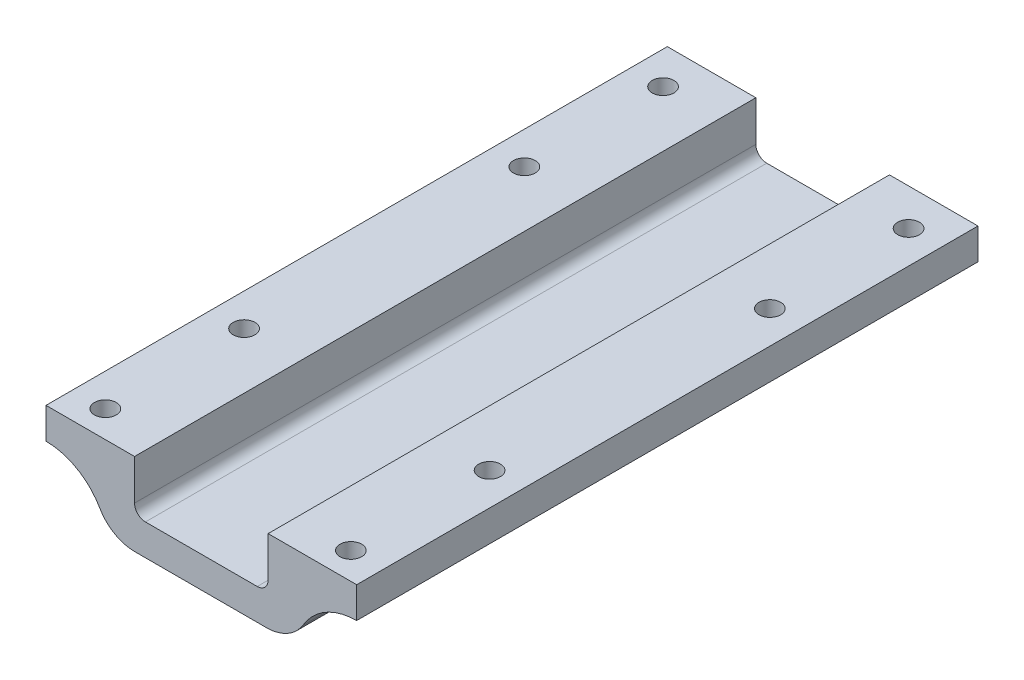
SolidWorks part; units mm, degrees
ref_plane "Front Plane" through (0, 0, 0) normal (0, 0, 1) x (1, 0, 0)
ref_plane "Top Plane" through (0, 0, 0) normal (0, 1, 0) x (1, 0, 0)
ref_plane "Right Plane" through (0, 0, 0) normal (1, 0, 0) x (0, 0, -1)
sketch "Sketch1" plane through (0, 0, 0) normal (0, 0, 1) x (1, 0, 0)
  line L0 (15, 13.2239) -> (35, 13.2239) construction
  line L1 (50, 10.2246) -> (50, 5.2246)
  line L2 (35.75, 10.2246) -> (50, 10.2246)
  line L3 (35.75, 3.7246) -> (35.75, 10.2246)
  line L4 (15, 22.2239) -> (15, 4.2239)
  line L5 (16, 3.2239) -> (34, 3.2239)
  line L6 (35, 4.2239) -> (35, 22.2239)
  line L7 (34, 23.2239) -> (16, 23.2239)
  line L8 (15, 22.2239) -> (15, 4.2239) construction
  line L9 (16, 3.2239) -> (34, 3.2239) construction
  line L10 (35, 4.2239) -> (35, 22.2239) construction
  line L11 (34, 23.2239) -> (16, 23.2239) construction
  line L12 (16, 1.9746) -> (34, 1.9746)
  line L13 (14.25, 10.2246) -> (14.25, 3.7246)
  line L14 (0, 10.2246) -> (14.25, 10.2246)
  line L15 (0, 5.2246) -> (0, 10.2246)
  line L16 (37.0096, 28.7233) -> (12.9904, 28.7233)
  line L17 (0, 21.2233) -> (0, 16.2233)
  line L18 (0, 16.2233) -> (14.25, 16.2233)
  line L19 (14.25, 16.2233) -> (14.25, 22.7233)
  line L20 (16, 24.4733) -> (34, 24.4733)
  line L21 (35.75, 22.7233) -> (35.75, 16.2233)
  line L22 (35.75, 16.2233) -> (50, 16.2233)
  line L23 (50, 16.2233) -> (50, 21.2233)
  line L24 (37.0096, 28.7233) -> (12.9904, 28.7233) construction
  line L25 (0, 21.2233) -> (0, 16.2233) construction
  line L26 (0, 16.2233) -> (14.25, 16.2233) construction
  line L27 (14.25, 16.2233) -> (14.25, 22.7233) construction
  line L28 (16, 24.4733) -> (34, 24.4733) construction
  line L29 (35.75, 22.7233) -> (35.75, 16.2233) construction
  line L30 (35.75, 16.2233) -> (50, 16.2233) construction
  line L31 (50, 16.2233) -> (50, 21.2233) construction
  line L33 (14.2894, -3.0254) -> (35.7106, -3.0254)
  arc A1 (41.3397, 0.2246) -> (50, 5.2246) centre (50, -4.7754) cw
  arc A2 (35.75, 3.7246) -> (34, 1.9746) centre (34, 3.7246) cw
  arc A3 (16, 1.9746) -> (14.25, 3.7246) centre (16, 3.7246) cw
  arc A4 (16, 23.2239) -> (15, 22.2239) centre (16, 22.2239) ccw
  arc A5 (15, 4.2239) -> (16, 3.2239) centre (16, 4.2239) ccw
  arc A6 (34, 3.2239) -> (35, 4.2239) centre (34, 4.2239) ccw
  arc A7 (35, 22.2239) -> (34, 23.2239) centre (34, 22.2239) ccw
  arc A8 (16, 23.2239) -> (15, 22.2239) centre (16, 22.2239) ccw construction
  arc A9 (15, 4.2239) -> (16, 3.2239) centre (16, 4.2239) ccw construction
  arc A10 (34, 3.2239) -> (35, 4.2239) centre (34, 4.2239) ccw construction
  arc A11 (35, 22.2239) -> (34, 23.2239) centre (34, 22.2239) ccw construction
  arc A12 (0, 5.2246) -> (8.6603, 0.2246) centre (0, -4.7754) cw
  arc A14 (12.9904, 28.7233) -> (8.6603, 26.2233) centre (12.9904, 23.7233) ccw
  arc A15 (0, 21.2233) -> (8.6603, 26.2233) centre (0, 31.2233) ccw
  arc A16 (16, 24.4733) -> (14.25, 22.7233) centre (16, 22.7233) ccw
  arc A17 (35.75, 22.7233) -> (34, 24.4733) centre (34, 22.7233) ccw
  arc A18 (41.3397, 26.2233) -> (50, 21.2233) centre (50, 31.2233) ccw
  arc A19 (41.3397, 26.2233) -> (37.0096, 28.7233) centre (37.0096, 23.7233) ccw
  arc A20 (12.9904, 28.7233) -> (8.6603, 26.2233) centre (12.9904, 23.7233) ccw construction
  arc A21 (0, 21.2233) -> (8.6603, 26.2233) centre (0, 31.2233) ccw construction
  arc A22 (16, 24.4733) -> (14.25, 22.7233) centre (16, 22.7233) ccw construction
  arc A23 (35.75, 22.7233) -> (34, 24.4733) centre (34, 22.7233) ccw construction
  arc A24 (41.3397, 26.2233) -> (50, 21.2233) centre (50, 31.2233) ccw construction
  arc A25 (41.3397, 26.2233) -> (37.0096, 28.7233) centre (37.0096, 23.7233) ccw construction
  arc A26 (8.6603, 0.2246) -> (14.2894, -3.0254) centre (14.2894, 3.4746) ccw
  arc A27 (35.7106, -3.0254) -> (41.3397, 0.2246) centre (35.4411, 3.9414) ccw
  point P52 (25, -3.0254)
  point P53 (25, 1.9746)
  dimension "D3" = 5
  dimension "D1" = 0
  dimension "D2" = 0
extrude "Boss-Extrude1" add sketch "Sketch1" against normal up to surface (100 mm away)
sketch "Sketch2" plane through (0, -3.0254, 0) normal (0, -1, 0) x (1, 0, 0)
  circle A0 centre (44.7568, -26.6349) radius 1.75 construction
  circle A1 centre (44.7568, -4.3068) radius 1.75 construction
  circle A2 centre (44.7568, -71.7427) radius 1.75 construction
  circle A3 centre (44.7568, -94.0708) radius 1.75 construction
  circle A4 centre (5.2432, -71.7427) radius 1.75 construction
  circle A5 centre (5.2432, -94.0708) radius 1.75 construction
  circle A6 centre (5.2432, -26.6349) radius 1.75 construction
  circle A7 centre (5.2432, -4.3068) radius 1.75 construction
  circle A8 centre (44.7568, -26.6349) radius 1.75
  circle A9 centre (44.7568, -4.3068) radius 1.75
  circle A10 centre (44.7568, -71.7427) radius 1.75
  circle A11 centre (44.7568, -94.0708) radius 1.75
  circle A12 centre (5.2432, -71.7427) radius 1.75
  circle A13 centre (5.2432, -94.0708) radius 1.75
  circle A14 centre (5.2432, -26.6349) radius 1.75
  circle A15 centre (5.2432, -4.3068) radius 1.75
extrude "Cut-Extrude1" cut sketch "Sketch2" against normal through all
sketch "Sketch3" plane through (0, -3.0254, 0) normal (0, -1, 0) x (1, 0, 0)
  line L0 (25, 0) -> (25, -100) construction
  line L1 (8.2432, -2.5748) -> (5.2432, -0.8427)
  line L2 (5.2432, -0.8427) -> (2.2432, -2.5748)
  line L3 (2.2432, -2.5748) -> (2.2432, -6.0389)
  line L4 (2.2432, -6.0389) -> (5.2432, -7.7709)
  line L5 (5.2432, -7.7709) -> (8.2432, -6.0389)
  line L6 (8.2432, -6.0389) -> (8.2432, -2.5748)
  line L7 (5.264, -23.1709) -> (2.2537, -24.8848)
  line L8 (2.2537, -24.8848) -> (2.2328, -28.3489)
  line L9 (2.2328, -28.3489) -> (5.2223, -30.0989)
  line L10 (5.2223, -30.0989) -> (8.2327, -28.385)
  line L11 (8.2327, -28.385) -> (8.2535, -24.9209)
  line L12 (8.2535, -24.9209) -> (5.264, -23.1709)
  line L13 (14.2894, 0) -> (35.7106, 0) construction
  line L14 (35.7106, -100) -> (14.2894, -100) construction
  line L15 (25, -100) -> (0, -50) construction
  line L16 (0, -100) -> (0, 0) construction
  line L17 (0, -50) -> (50, -50) construction
  line L18 (50, -100) -> (50, 0) construction
  line L19 (41.7465, -24.9209) -> (44.736, -23.1709)
  line L20 (41.7673, -28.385) -> (41.7465, -24.9209)
  line L21 (44.7777, -30.0989) -> (41.7673, -28.385)
  line L22 (47.7672, -28.3489) -> (44.7777, -30.0989)
  line L23 (47.7463, -24.8848) -> (47.7672, -28.3489)
  line L24 (44.736, -23.1709) -> (47.7463, -24.8848)
  line L25 (41.7568, -6.0389) -> (41.7568, -2.5748)
  line L26 (44.7568, -7.7709) -> (41.7568, -6.0389)
  line L27 (47.7568, -6.0389) -> (44.7568, -7.7709)
  line L28 (47.7568, -2.5748) -> (47.7568, -6.0389)
  line L29 (44.7568, -0.8427) -> (47.7568, -2.5748)
  line L30 (41.7568, -2.5748) -> (44.7568, -0.8427)
  line L31 (41.7568, -92.3387) -> (44.7568, -90.6067)
  line L32 (5.2516, -68.2786) -> (2.2474, -70.0033)
  line L33 (2.2474, -70.0033) -> (2.239, -73.4674)
  line L34 (2.239, -73.4674) -> (5.2347, -75.2068)
  line L35 (5.2347, -75.2068) -> (8.2389, -73.482)
  line L36 (8.2389, -73.482) -> (8.2474, -70.018)
  line L37 (8.2474, -70.018) -> (5.2516, -68.2786)
  line L38 (5.2432, -90.6067) -> (2.2432, -92.3387)
  line L39 (2.2432, -92.3387) -> (2.2432, -95.8028)
  line L40 (2.2432, -95.8028) -> (5.2432, -97.5349)
  line L41 (5.2432, -97.5349) -> (8.2432, -95.8028)
  line L42 (8.2432, -95.8028) -> (8.2432, -92.3387)
  line L43 (8.2432, -92.3387) -> (5.2432, -90.6067)
  line L44 (41.7568, -95.8028) -> (41.7568, -92.3387)
  line L45 (44.7568, -97.5349) -> (41.7568, -95.8028)
  line L46 (47.7568, -95.8028) -> (44.7568, -97.5349)
  line L47 (47.7568, -92.3387) -> (47.7568, -95.8028)
  line L48 (44.7568, -90.6067) -> (47.7568, -92.3387)
  line L49 (41.7526, -70.018) -> (44.7484, -68.2786)
  line L50 (41.7611, -73.482) -> (41.7526, -70.018)
  line L51 (44.7653, -75.2068) -> (41.7611, -73.482)
  line L52 (47.761, -73.4674) -> (44.7653, -75.2068)
  line L53 (47.7526, -70.0033) -> (47.761, -73.4674)
  line L54 (44.7484, -68.2786) -> (47.7526, -70.0033)
  circle A0 centre (5.2432, -4.3068) radius 3 construction
  circle A1 centre (5.2432, -26.6349) radius 3 construction
  circle A2 centre (44.7568, -26.6349) radius 3 construction
  circle A3 centre (44.7568, -4.3068) radius 3 construction
  circle A4 centre (5.2432, -71.7427) radius 3 construction
  circle A5 centre (5.2432, -94.0708) radius 3 construction
  circle A6 centre (44.7568, -94.0708) radius 3 construction
  circle A7 centre (44.7568, -71.7427) radius 3 construction
  dimension "D1" = 6
extrude "Cut-Extrude2" cut sketch "Sketch3" against normal up to vertex (8.25 mm away) up to point (0, 5.2246, -100)
